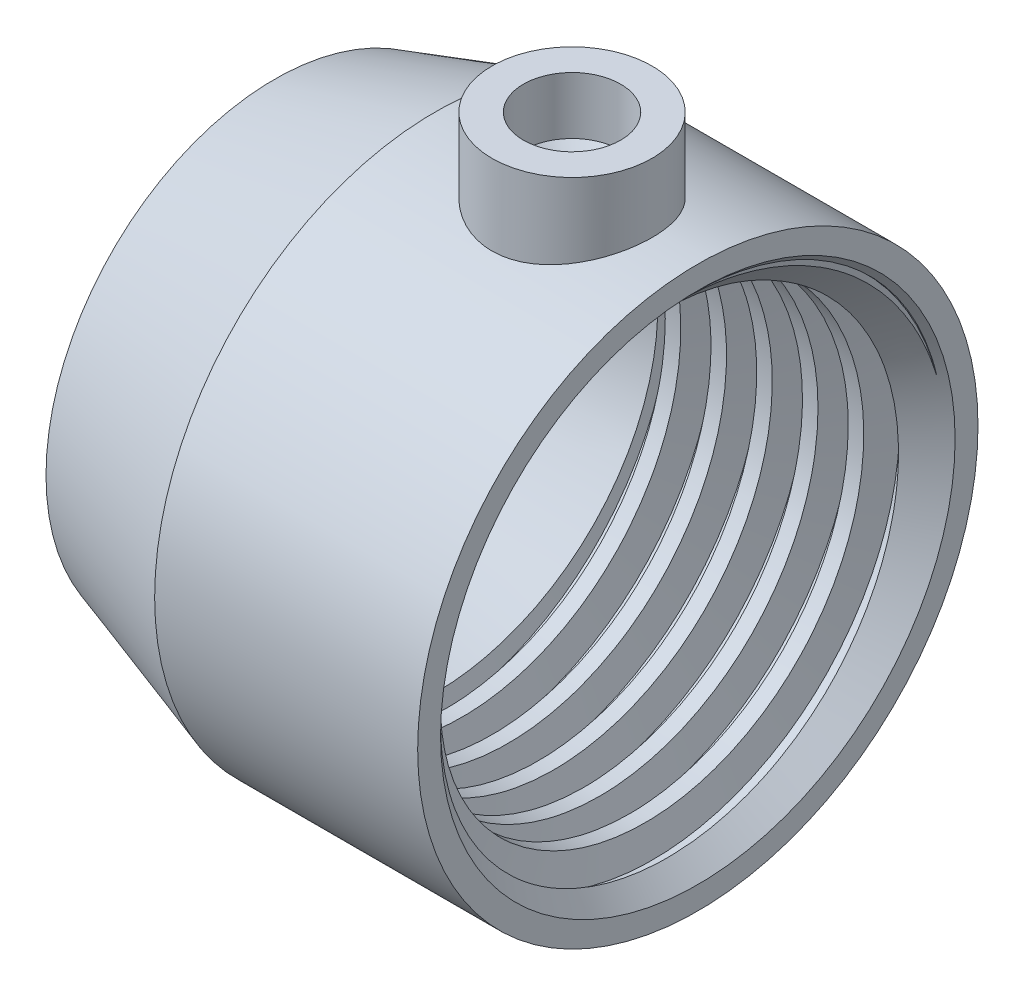
SolidWorks part; units mm, degrees
ref_plane "Front Plane" through (0, 0, 0) normal (0, 0, 1) x (1, 0, 0)
ref_plane "Top Plane" through (0, 0, 0) normal (0, 1, 0) x (1, 0, 0)
ref_plane "Right Plane" through (0, 0, 0) normal (1, 0, 0) x (0, 0, -1)
sketch "Sketch1" plane through (0, 0, 0) normal (0, 0, 1) x (1, 0, 0)
  line L0 (0, 13.5) -> (0, 20)
  line L1 (0, 20) -> (14, 24.5)
  line L2 (14, 24.5) -> (37, 24.5)
  line L3 (37, 24.5) -> (37, 19.5)
  line L4 (37, 19.5) -> (14, 19.5)
  line L5 (14, 19.5) -> (3, 15.9643)
  line L6 (3, 15.9643) -> (3, 13.5)
  line L7 (3, 13.5) -> (0, 13.5)
  line L8 (0, 0) -> (49.8966, 0) construction
  dimension "D1" = 37
  dimension "D2" = 3
  dimension "D3" = 11
  dimension "D4" = 13.5
  dimension "D5" = 24.5
  dimension "D6" = 20
  dimension "D7" = 19.5
revolve "Revolve1" add sketch "Sketch1" angle 360 about L8
chamfer "Chamfer1" distance 3 angle 45 1 edges at (37, 0, 19.5)
sketch "Sketch3" plane through (37, 0, 0) normal (1, 0, 0) x (0, 0, -1)
  circle A1 centre (0, 0) radius 24.5
  circle A2 centre (0, 0) radius 24.5
  dimension "D1" = 0
sketch "Sketch7" plane through (37, 0, 0) normal (1, 0, 0) x (0, 0, -1)
  circle A0 centre (0, 0) radius 19.5 construction
  circle A1 centre (0, 0) radius 19.5
curve "Helix/Spiral2" pitch 4 height 23 turns 5.75
sketch "Sketch9" plane through (0, 0, 0) normal (0, 0, 1) x (1, 0, 0)
  line L0 (37, -19.5) -> (39.6431, -19.5)
  line L1 (39.6431, -19.5) -> (38.9965, -22)
  line L2 (38.9965, -22) -> (37.6465, -22)
  line L3 (37.6465, -22) -> (37, -19.5)
  line L4 (38.3215, -22) -> (38.3215, 1.9462) construction
  line L5 (14, -19.5) -> (34, -19.5) construction
  spline S0 degree 3 poles (37, -19.5) (36.9318, -19.5) (36.7945, -18.8178) (36.5893, -15.8533) (36.3839, -11.2534) (36.1786, -5.4927) (35.9732, 0.8346) (35.7679, 7.0758) (35.5625, 12.5871) (35.3571, 16.8) (35.1518, 19.2798) (34.9464, 19.7709) (34.7411, 18.2225) (34.5357, 14.7944) (34.3304, 9.8401) (34.125, 3.8708) (33.9196, -2.4978) (33.7143, -8.6087) (33.5089, -13.8316) (33.3036, -17.6278) (33.0982, -19.6055) (32.8929, -19.5608) (32.6875, -17.4983) (32.4821, -13.6308) (32.2768, -8.3572) (32.0714, -2.2215) (31.8661, 4.1433) (31.6607, 10.0808) (31.4554, 14.9783) (31.25, 18.3308) (31.0446, 19.7924) (30.8393, 19.2122) (30.6339, 16.6503) (30.4286, 12.3707) (30.2232, 6.8151) (30.0179, 0.5565) (29.8125, -5.7596) (29.6071, -11.4815) (29.4018, -16.019) (29.1964, -18.9041) (28.9911, -19.8392) (28.7857, -18.7277) (28.5804, -15.6844) (28.375, -11.0231) (28.1696, -5.2248) (27.9643, 1.1125) (27.7589, 7.335) (27.5536, 12.8009) (27.3482, 16.9463) (27.1429, 19.3437) (26.9375, 19.7456) (26.7321, 18.1106) (26.5268, 14.6075) (26.3214, 9.5975) (26.1161, 3.5975) (25.9107, -2.7736) (25.7054, -8.8586) (25.5, -14.0298) (25.2946, -17.7537) (25.0893, -19.6463) (24.8839, -19.5122) (24.6786, -17.3654) (24.4732, -13.4272) (24.2679, -8.104) (24.0625, -1.9448) (23.8571, 4.4151) (23.6518, 10.3195) (23.4464, 15.1594) (23.2411, 18.4355) (23.0357, 19.8099) (22.8304, 19.1408) (22.625, 16.4973) (22.4196, 12.152) (22.2143, 6.5531) (22.0089, 0.2783) (21.8036, -6.0253) (21.5982, -11.7073) (21.3929, -16.1816) (21.1875, -18.9868) (20.9821, -19.8333) (20.7768, -18.634) (20.5714, -15.5124) (20.3661, -10.7907) (20.1607, -4.9558) (19.9554, 1.3902) (19.75, 7.5929) (19.5446, 13.0123) (19.3393, 17.0894) (19.1339, 19.4037) (18.9286, 19.7164) (18.7232, 17.9952) (18.5179, 14.4178) (18.3125, 9.353) (18.1071, 3.3235) (17.9018, -3.0489) (17.6964, -9.1067) (17.4911, -14.2252) (17.2857, -17.8762) (17.0804, -19.6833) (16.875, -19.4599) (16.6696, -17.2291) (16.4643, -13.2211) (16.2589, -7.8492) (16.0536, -1.6677) (15.8482, 4.6859) (15.6429, 10.5561) (15.4375, 15.3374) (15.2321, 18.5365) (15.0268, 19.8236) (14.8214, 19.0656) (14.6161, 16.3414) (14.4107, 11.9297) (14.2055, 6.294) (14.0682, 2.0877) (14, 0) knots 0 0 0 0 0.008929 0.017857 0.026786 0.035714 0.044643 0.053571 0.0625 0.071429 0.080357 0.089286 0.098214 0.107143 0.116071 0.125 0.133929 0.142857 0.151786 0.160714 0.169643 0.178571 0.1875 0.196429 0.205357 0.214286 0.223214 0.232143 0.241071 0.25 0.258929 0.267857 0.276786 0.285714 0.294643 0.303571 0.3125 0.321429 0.330357 0.339286 0.348214 0.357143 0.366071 0.375 0.383929 0.392857 0.401786 0.410714 0.419643 0.428571 0.4375 0.446429 0.455357 0.464286 0.473214 0.482143 0.491071 0.5 0.508929 0.517857 0.526786 0.535714 0.544643 0.553571 0.5625 0.571429 0.580357 0.589286 0.598214 0.607143 0.616071 0.625 0.633929 0.642857 0.651786 0.660714 0.669643 0.678571 0.6875 0.696429 0.705357 0.714286 0.723214 0.732143 0.741071 0.75 0.758929 0.767857 0.776786 0.785714 0.794643 0.803571 0.8125 0.821429 0.830357 0.839286 0.848214 0.857143 0.866071 0.875 0.883929 0.892857 0.901786 0.910714 0.919643 0.928571 0.9375 0.946429 0.955357 0.964286 0.973214 0.982143 0.991071 1 1 1 1 construction
  point P8 (38.3215, -19.5)
  point P12 (0, 0)
  dimension "D1" = 29
  dimension "D2" = 2.5
  dimension "D3" = 1.35
sweep "Cut-Sweep4" cut profiles "Sketch9" path "Helix/Spiral2"
ref_plane "Plane1" through (0, 30.5, 0) normal (0, 1, 0) x (1, 0, 0)
sketch "Sketch11" plane through (0, 30.5, 0) normal (0, 1, 0) x (1, 0, 0)
  line L0 (37, -24.5) -> (37, 24.5) construction
  circle A0 centre (26, 0) radius 7
  dimension "D1" = 14
  dimension "D2" = 11
extrude "Boss-Extrude1" add sketch "Sketch11" against normal up to surface (7.0213 mm away)
hole_wizard "M10x1.5 Tapped Hole1" positions "Sketch15" profile "Sketch16" tap size "M10x1.5" standard "ANSI Metric"
sketch "Sketch15" plane through (0, 30.5, 0) normal (0, 1, 0) x (1, 0, 0)
  point P0 (26, 0)
sketch "Sketch16" plane through (26, 30.5, 0) normal (1, 0, 0) x (0, 0, 1)
  line L0 (0, 0) -> (0, 9.25)
  line L1 (0, 9.25) -> (4.25, 5)
  line L2 (4.25, 5) -> (4.25, 0)
  line L5 (4.25, 0) -> (0, 0)
  line L10 (0, 9.25) -> (-4.25, 5) construction
  line L11 (0, -6.35) -> (0, 107.95) construction
  dimension "Tap Drill Dia." = 8.5
  dimension "Tap Drill Depth" = 5
  dimension "Drill Angle" = 90
cosmetic thread "Hole Thread1" parameters "D1"=3.5, "D2"=10
